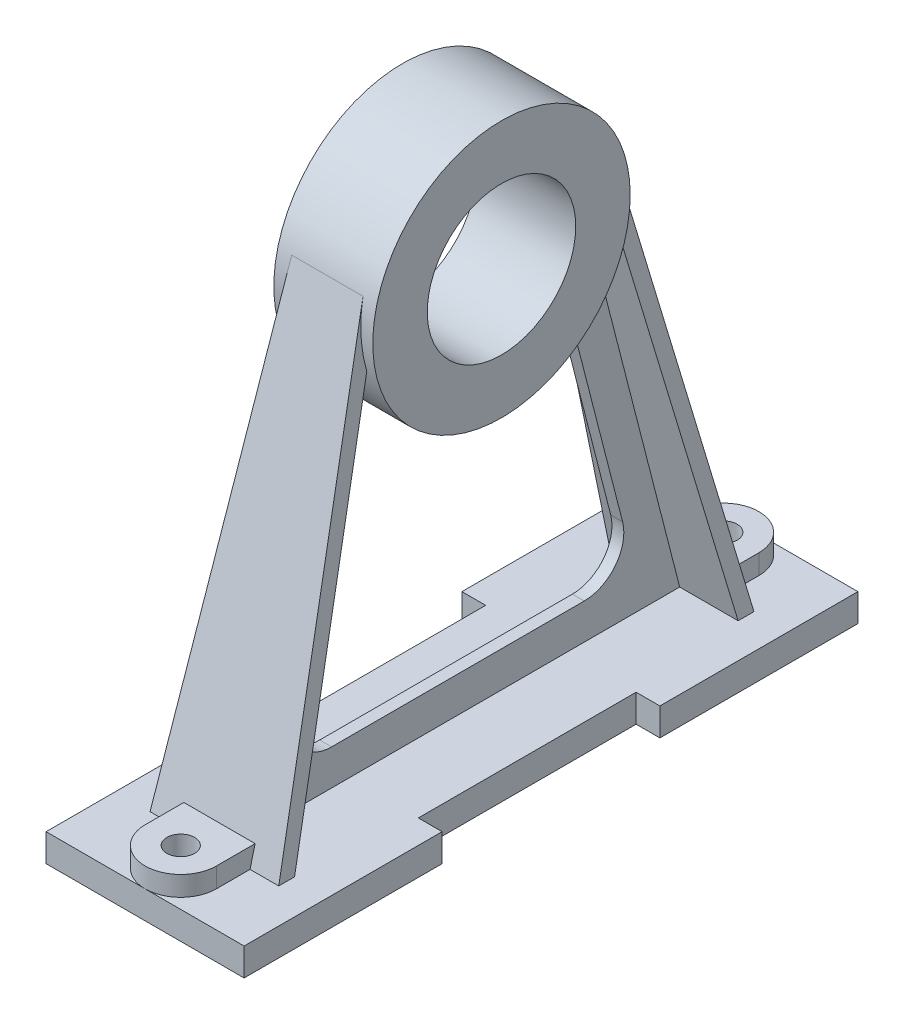
SolidWorks part; units mm, degrees
ref_plane "Front Plane" through (0, 0, 0) normal (0, 0, 1) x (1, 0, 0)
ref_plane "Top Plane" through (0, 0, 0) normal (0, 1, 0) x (1, 0, 0)
ref_plane "Right Plane" through (0, 0, 0) normal (1, 0, 0) x (0, 0, -1)
sketch "Sketch1" plane through (0, 0, 0) normal (0, 0, 1) x (1, 0, 0)
  line L1 (-50, 0) -> (50, 0)
  line L2 (-50, 0) -> (-50, 14)
  line L3 (-50, 14) -> (50, 14)
  line L4 (50, 0) -> (50, 14)
  point P5 (0, 0)
  dimension "D1" = 100
  dimension "D2" = 14
extrude "Boss-Extrude1" add sketch "Sketch1" against normal blind 310
sketch "Sketch2" plane through (0, 14, 0) normal (0, 1, 0) x (1, 0, 0)
  line L0 (50, 310) -> (50, 0) construction
  line L1 (50, 210) -> (38, 210)
  line L2 (50, 210) -> (50, 100)
  line L3 (50, 100) -> (38, 100)
  line L4 (38, 210) -> (38, 100)
  line L5 (0, 0) -> (0, 95.6534) construction
  line L6 (50, 0) -> (-50, 0) construction
  line L7 (50, 310) -> (-50, 310) construction
  line L8 (-50, 100) -> (-38, 100)
  line L9 (-38, 210) -> (-38, 100)
  line L10 (-50, 210) -> (-38, 210)
  line L11 (-50, 210) -> (-50, 100)
  dimension "D1" = 100
  dimension "D2" = 100
  dimension "D3" = 12
extrude "Cut-Extrude1" cut sketch "Sketch2" against normal through all
sketch "Sketch3" plane through (0, 0, 0) normal (1, 0, 0) x (0, 0, -1)
  line L0 (310, 0) -> (210, 0) construction
  line L1 (210, 14) -> (100, 14) construction
  circle A0 centre (155, 220) radius 65
  circle A1 centre (155, 220) radius 37.5
  point P7 (155, 14)
  dimension "D1" = 220
  dimension "D2" = 130
  dimension "D3" = 75
extrude "Boss-Extrude2" add sketch "Sketch3" along normal mid plane 50 separate body
sketch "Sketch4" plane through (0, 0, 0) normal (1, 0, 0) x (0, 0, -1)
  line L0 (35, 14) -> (92.0421, 236.1648)
  line L1 (100, 14) -> (0, 14) construction
  line L2 (0, 0) -> (0, 14) construction
  line L3 (155, 220) -> (155, 75.654) construction
  line L4 (275, 14) -> (217.9579, 236.1648)
  line L5 (244.5675, 32) -> (206.4849, 180.3224)
  line L6 (250.7854, 7.7828) -> (193.7433, 229.9476) construction
  line L7 (65.4325, 32) -> (103.5151, 180.3224)
  line L8 (35, 14) -> (275, 14)
  line L9 (65.4325, 32) -> (244.5675, 32)
  circle A0 centre (155, 220) radius 65 construction
  arc A1 (92.0421, 236.1648) -> (103.5151, 180.3224) centre (155, 220) ccw
  arc A2 (206.4849, 180.3224) -> (217.9579, 236.1648) centre (155, 220) ccw
  point P11 (0, 0)
  dimension "D1" = 35
  dimension "D3" = 18
  dimension "D2" = 25
extrude "Boss-Extrude4" add sketch "Sketch4" along normal mid plane 6 contours L5 A2 L4 L8 L0 A1 L7 L9
fillet "Fillet1" radius 20 2 edges at (0, 32, -65.4325) (0, 32, -244.5675)
ref_plane "Plane1" through (0, 0, -155) normal (0, 0, 1) x (1, 0, 0)
sketch "Sketch7" plane through (0, 0, -155) normal (0, 0, 1) x (1, 0, 0)
  line L0 (-32.5, 14) -> (-18, 236.1648)
  line L1 (50, 14) -> (-50, 14) construction
  line L2 (32.5, 14) -> (18, 236.1648)
  line L3 (0, 0) -> (0, 29.6726) construction
  line L4 (3, 236.1648) -> (-3, 236.1648) construction
  line L5 (-18, 236.1648) -> (18, 236.1648)
  line L6 (-32.5, 14) -> (32.5, 14)
  dimension "D1" = 65
  dimension "D2" = 36
extrude "Boss-Extrude5" add sketch "Sketch7" against normal blind 8 from surface starting at face at (0, 125.0824, -63.521)
extrude "Boss-Extrude6" add sketch "Sketch7<2>" along normal blind 8 from surface starting at face at (0, 125.0824, -246.479)
sketch "Sketch7<2>" plane through (0, 0, -155) normal (0, 0, 1) x (1, 0, 0) same geometry as "Sketch7"
sketch "Sketch8" plane through (0, 14, 0) normal (0, 1, 0) x (1, 0, 0)
  line L0 (-18, 275) -> (-18, 292)
  line L1 (32.5, 275) -> (-32.5, 275) construction
  line L2 (18, 292) -> (18, 275)
  line L3 (18, 275) -> (-18, 275)
  line L4 (50, 310) -> (-50, 310) construction
  line L6 (-38, 155) -> (38, 155) construction
  line L7 (-38, 100) -> (-38, 210) construction
  line L8 (38, 210) -> (38, 100) construction
  line L9 (18, 18) -> (18, 35)
  line L10 (-18, 35) -> (-18, 18)
  line L11 (18, 35) -> (-18, 35)
  arc A0 (-18, 292) -> (18, 292) centre (0, 292) cw
  circle A1 centre (0, 292) radius 7
  circle A2 centre (0, 18) radius 7
  arc A3 (-18, 18) -> (18, 18) centre (0, 18) ccw
  point P10 (0, 275)
  dimension "D1" = 14
  dimension "D2" = 18
extrude "Boss-Extrude7" add sketch "Sketch8" along normal blind 10
sketch "Sketch9" plane through (0, 0, -275) normal (0, 0, 1) x (1, 0, 0)
  line L4 (-18, 14) -> (18, 14)
  line L5 (18, 14) -> (18, 24)
  line L6 (18, 24) -> (-18, 24)
  line L7 (-18, 24) -> (-18, 14)
  line L8 (-18, 14) -> (18, 14)
  line L9 (18, 14) -> (18, 24)
  line L10 (18, 24) -> (-18, 24)
  line L11 (-18, 24) -> (-18, 14)
  dimension "D1" = 0
extrude "Boss-Extrude8" add sketch "Sketch9" along normal up to next
sketch "Sketch10" plane through (0, 0, -35) normal (0, 0, -1) x (-1, 0, 0)
  line L4 (-18, 14) -> (18, 14)
  line L5 (18, 14) -> (18, 24)
  line L6 (18, 24) -> (-18, 24)
  line L7 (-18, 24) -> (-18, 14)
  line L8 (-18, 14) -> (18, 14)
  line L9 (18, 14) -> (18, 24)
  line L10 (18, 24) -> (-18, 24)
  line L11 (-18, 24) -> (-18, 14)
  dimension "D1" = 0
extrude "Boss-Extrude9" add sketch "Sketch10" along normal up to next
sketch "Sketch11" plane through (-25, 0, 0) normal (-1, 0, 0) x (0, 0, 1)
  line L0 (-155, 220) -> (-155, 272.5) construction
  line L2 (-155, 220) -> (-117.8769, 257.1231) construction
  circle A0 centre (-155, 220) radius 52.5 construction
  point P12 (-117.8769, 257.1231)
  point P22 (-117.8769, 182.8769)
  point P23 (-192.1231, 182.8769)
  point P24 (-192.1231, 257.1231)
  point P25 (-117.8769, 257.1231)
  dimension "D1" = 105
  dimension "D2" = 45
  dimension "D3" = 4
hole_wizard "M6 Tapped Hole1" positions "Sketch11" profile "Sketch12" tap size "M6" standard "ISO"
sketch "Sketch12" plane through (-25, 257.1231, -117.8769) normal (0, 1, 0) x (0, 0, 1)
  line L0 (0, 0) -> (0, 12)
  line L1 (0, 12) -> (2.5, 12)
  line L2 (2.5, 12) -> (2.5, 0)
  line L5 (2.5, 0) -> (0, 0)
  line L10 (0, 12) -> (-2.5, 12) construction
  line L11 (0, -6.35) -> (0, 107.95) construction
  dimension "Tap Drill Dia." = 5
  dimension "Tap Drill Depth" = 12
  dimension "Drill Angle" = 180
cosmetic thread "Hole Thread1" parameters "D1"=12, "D2"=6
cosmetic thread "Hole Thread2" parameters "D1"=12, "D2"=6
cosmetic thread "Hole Thread3" parameters "D1"=12, "D2"=6
cosmetic thread "Hole Thread4" parameters "D1"=12, "D2"=6
